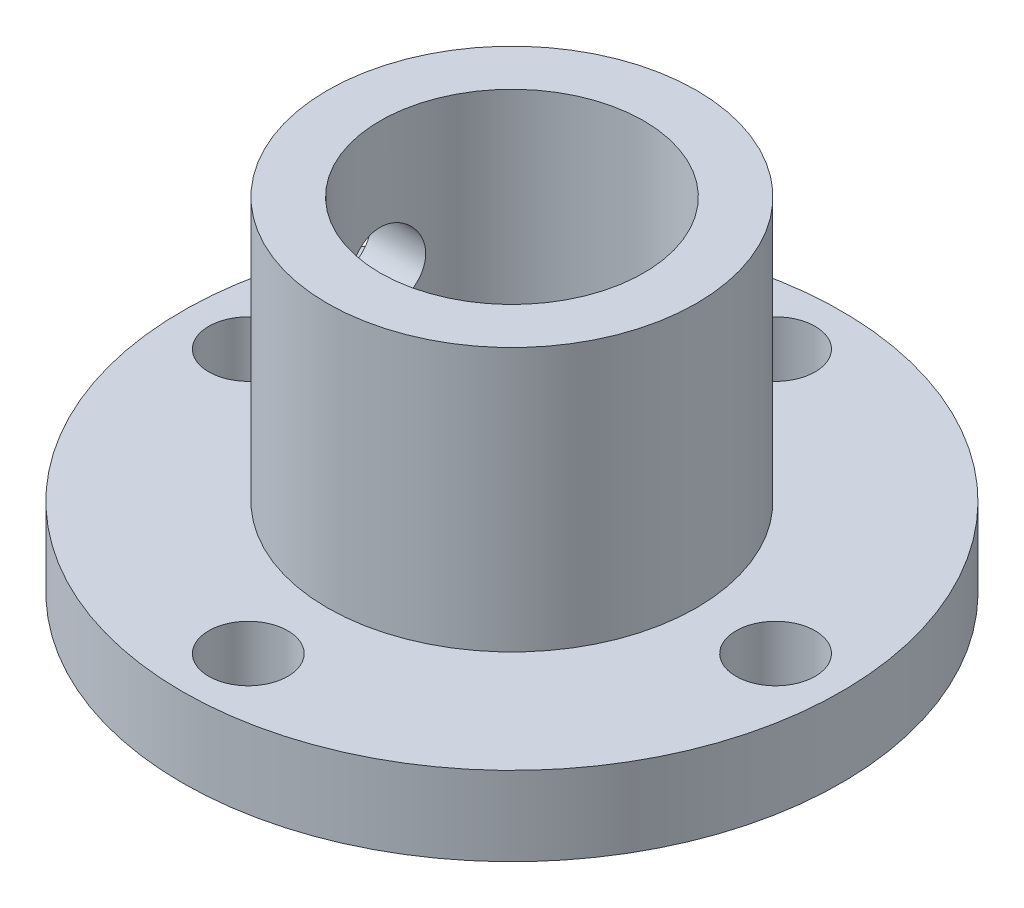
SolidWorks part; units mm, degrees
ref_plane "Ön Düzlem" through (0, 0, 0) normal (0, 0, 1) x (1, 0, 0)
ref_plane "Üst Düzlem" through (0, 0, 0) normal (0, 1, 0) x (1, 0, 0)
ref_plane "Sağ Düzlem" through (0, 0, 0) normal (1, 0, 0) x (0, 0, -1)
sketch "Çizim1" plane through (0, 0, 0) normal (0, 1, 0) x (1, 0, 0)
  circle A0 centre (0, 0) radius 12.5
  circle A1 centre (0, 0) radius 10 construction
  circle A2 centre (10, 0) radius 1.5
  circle A3 centre (0, -10) radius 1.5
  circle A4 centre (-10, 0) radius 1.5
  circle A5 centre (0, 10) radius 1.5
  point P15 (0, 0)
  dimension "D2" = 3
  dimension "D3" = 25
  dimension "D4" = 20
  dimension "D1" = 4
extrude "Yükseklik-Ekstrüzyon1" add sketch "Çizim1" along normal blind 3
sketch "Çizim2" plane through (0, 3, 0) normal (0, 1, 0) x (1, 0, 0)
  circle A0 centre (0, 0) radius 5
  dimension "D1" = 10
extrude "Ekstrüzyon-İnce1" add sketch "Çizim2" along normal blind 10 thin thin type one direction wall 2
sketch "Çizim3" plane through (0, 0, 0) normal (1, 0, 0) x (0, 0, -1)
  line L0 (0, 13) -> (0, 3) construction
  line L1 (7, 13) -> (-7, 13) construction
  line L2 (12.5, 3) -> (-12.5, 3) construction
  circle A0 centre (0, 8) radius 1.5
  dimension "D1" = 3
extrude "Kes-Ekstrüzyon1" cut sketch "Çizim3" against normal through all
extrude "Kes-Ekstrüzyon2" cut sketch "Çizim2<2>" against normal through all
sketch "Çizim2<2>" plane through (0, 3, 0) normal (0, 1, 0) x (1, 0, 0) same geometry as "Çizim2"
